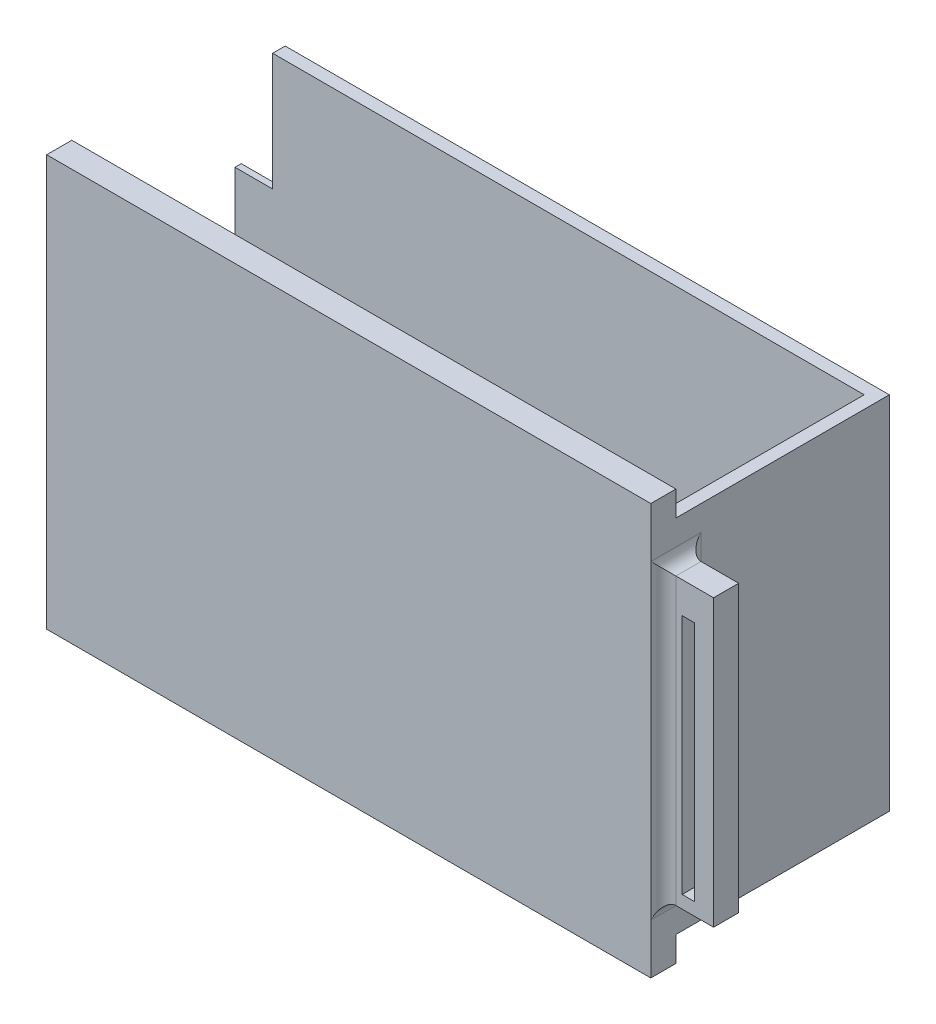
SolidWorks part; units mm, degrees
ref_plane "Front Plane" through (0, 0, 0) normal (0, 0, 1) x (1, 0, 0)
ref_plane "Top Plane" through (0, 0, 0) normal (0, 1, 0) x (1, 0, 0)
ref_plane "Right Plane" through (0, 0, 0) normal (1, 0, 0) x (0, 0, -1)
sketch "Sketch2" plane through (0, 0, 0) normal (1, 0, 0) x (0, 0, -1)
  line L0 (-1238.5207, 790.6854) -> (-1238.5207, 788.6854)
  line L1 (-1240.5207, 790.6854) -> (-1238.5207, 790.6854)
  line L2 (-1240.5207, 790.6854) -> (-1240.5207, 757.9554)
  line L3 (-1240.5207, 757.9554) -> (-1238.5207, 757.9554)
  line L5 (-1238.5207, 788.6854) -> (-1221.5207, 788.6854)
  line L7 (-1238.5207, 759.9554) -> (-1221.5207, 759.9554)
  line L8 (-1221.5207, 788.6854) -> (-1221.5207, 759.9554)
  line L9 (-1238.5207, 759.9554) -> (-1238.5207, 757.9554)
  dimension "D1" = 2
  dimension "D2" = 32.73
  dimension "D3" = 17
  dimension "D4" = 28.73
  dimension "D5" = 2
  dimension "D6" = 2
extrude "Boss-Extrude1" add sketch "Sketch2" against normal blind 48.12
sketch "Sketch3" plane through (-48.12, 0, 0) normal (-1, 0, 0) x (0, 0, 1)
  line L0 (1221.5207, 788.6854) -> (1238.5207, 788.6854) construction
  line L1 (1222.5207, 788.6854) -> (1238.5207, 788.6854)
  line L2 (1222.5207, 788.6854) -> (1222.5207, 759.9554)
  line L3 (1222.5207, 759.9554) -> (1238.5207, 759.9554)
  line L4 (1238.5207, 788.6854) -> (1238.5207, 759.9554)
  line L5 (1238.5207, 759.9554) -> (1221.5207, 759.9554) construction
  line L7 (1240.5207, 790.6854) -> (1240.5207, 757.9554) construction
  line L8 (1221.5207, 759.9554) -> (1221.5207, 788.6854) construction
  dimension "D1" = 2
  dimension "D2" = 1
extrude "Cut-Extrude1" cut sketch "Sketch3" against normal blind 47.12
sketch "Sketch4" plane through (-48.12, 0, 0) normal (-1, 0, 0) x (0, 0, 1)
  line L0 (1222.5207, 788.6854) -> (1222.5207, 759.9554) construction
  line L1 (1222.5207, 779.3204) -> (1222.0207, 779.3204)
  line L2 (1222.5207, 779.3204) -> (1222.5207, 769.3204)
  line L3 (1222.5207, 769.3204) -> (1222.0207, 769.3204)
  line L4 (1222.0207, 779.3204) -> (1222.0207, 769.3204)
  line L5 (1221.5207, 788.6854) -> (1222.5207, 788.6854) construction
  dimension "D1" = 0.5
  dimension "D2" = 9.365
  dimension "D3" = 10
extrude "Boss-Extrude2" add sketch "Sketch4" along normal blind 3
sketch "Sketch5" plane through (0, 0, 0) normal (1, 0, 0) x (0, 0, -1)
  line L0 (-1221.5207, 788.6854) -> (-1238.5207, 788.6854) construction
  line L1 (-1239.5207, 785.6854) -> (-1237.5207, 785.6854)
  line L2 (-1239.5207, 785.6854) -> (-1239.5207, 762.9554)
  line L3 (-1239.5207, 762.9554) -> (-1237.5207, 762.9554)
  line L4 (-1237.5207, 785.6854) -> (-1237.5207, 762.9554)
  line L5 (-1238.5207, 759.9554) -> (-1221.5207, 759.9554) construction
  line L6 (-1240.5207, 790.6854) -> (-1240.5207, 757.9554) construction
  dimension "D1" = 3
  dimension "D2" = 3
  dimension "D3" = 1
  dimension "D4" = 2
extrude "Boss-Extrude3" add sketch "Sketch5" along normal blind 4
sketch "Sketch6" plane through (0, 0, 1239.5207) normal (0, 0, 1) x (1, 0, 0)
  line L0 (0, 785.6854) -> (0, 762.9554) construction
  line L1 (1.5, 783.1979) -> (2.5, 783.1979)
  line L2 (1.5, 783.1979) -> (1.5, 763.9673)
  line L3 (1.5, 763.9673) -> (2.5, 763.9673)
  line L4 (2.5, 783.1979) -> (2.5, 763.9673)
  dimension "D1" = 1.5
  dimension "D2" = 1
extrude "Cut-Extrude2" cut sketch "Sketch6" against normal blind 1
fillet "Fillet1" radius 1 1 edges at (0, 774.3204, 1239.5207) type face fillet first side face at (2, 773.5826, 1239.5207) second side face at (0, 774.3204, 1234.7707)
fillet "Fillet2" radius 1 1 edges at (0, 774.3204, 1237.5207) type face fillet first side face at (2, 774.3204, 1237.5207) second side face at (0, 774.3204, 1236.1874)
fillet "Fillet3" radius 1 1 edges at (0, 785.6854, 1238.5207) type face fillet first side face at (0, 774.3204, 1236.0207) second side face at (1.5976, 785.6854, 1238.5207)
fillet "Fillet4" radius 1 1 edges at (0, 762.9554, 1238.5207) type face fillet first side face at (1.5976, 762.9554, 1238.5207) second side face at (0, 774.487, 1236.0207)
